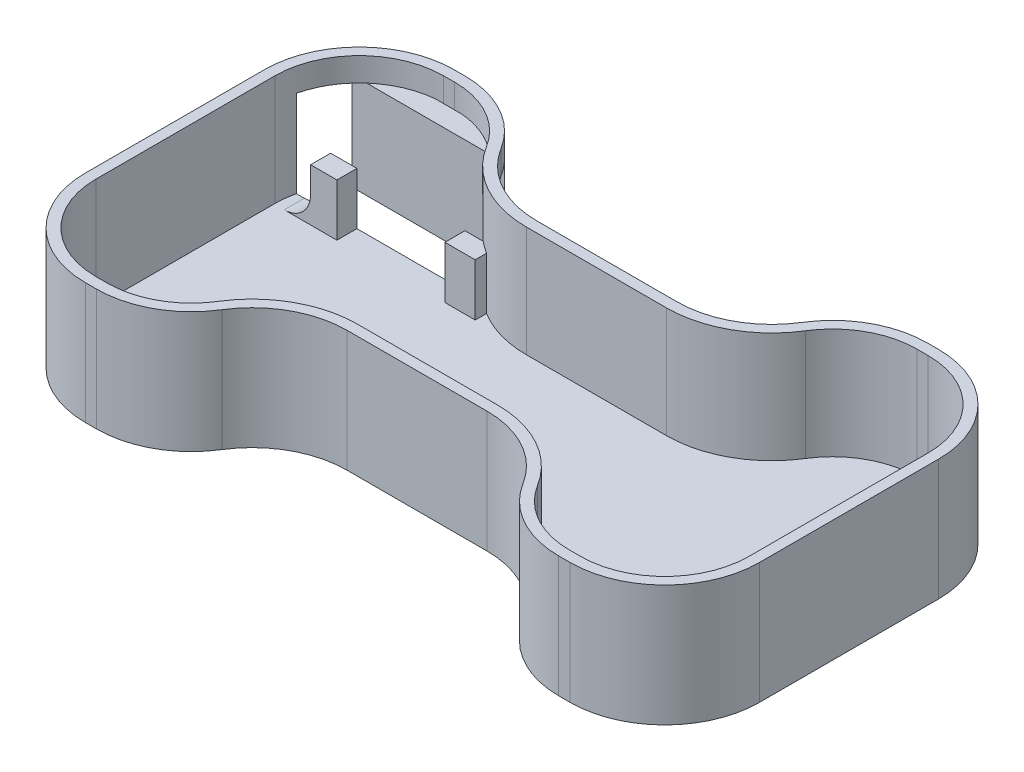
SolidWorks part; units mm, degrees
ref_plane "Front Plane" through (0, 0, 0) normal (0, 0, 1) x (1, 0, 0)
ref_plane "Top Plane" through (0, 0, 0) normal (0, 1, 0) x (1, 0, 0)
ref_plane "Right Plane" through (0, 0, 0) normal (1, 0, 0) x (0, 0, -1)
sketch "Sketch1" plane through (0, 0, 0) normal (0, 1, 0) x (1, 0, 0)
  line L0 (-128, 70) -> (-128, -70)
  line L1 (-128, 70) -> (-51.8, 70)
  line L2 (-51.8, 70) -> (-51.8, 36)
  line L3 (-51.8, 36) -> (51.8, 36)
  line L6 (51.8, 70) -> (51.8, 36)
  line L7 (128, 70) -> (51.8, 70)
  line L8 (128, 70) -> (128, -70)
  line L9 (-51.8, -70) -> (-51.8, -36)
  line L10 (-128, -70) -> (-51.8, -70)
  line L11 (128, -70) -> (51.8, -70)
  line L12 (51.8, -70) -> (51.8, -36)
  line L13 (-51.8, -36) -> (51.8, -36)
  dimension "D3" = 76.2
  dimension "D2" = 140
  dimension "D1" = 256
  dimension "D4" = 128
  dimension "D5" = 76.2
  dimension "D6" = 76.2
  dimension "D7" = 76.2
  dimension "D8" = 70
  dimension "D9" = 0
extrude "Boss-Extrude1" add sketch "Sketch1" along normal blind 4
fillet "Fillet2" radius 36 8 edges at (-51.8, 2, -70) (-128, 2, -70) (-128, 2, 70) (-51.8, 2, 70) (51.8, 2, -70) (128, 2, -70) (128, 2, 70) (51.8, 2, 70)
fillet "Fillet3" radius 36 4 edges at (-51.8, 2, -36) (-51.8, 2, 36) (51.8, 2, 36) (51.8, 2, -36)
sketch "Sketch2" plane through (0, 4, 0) normal (0, 1, 0) x (1, 0, 0)
  line L34 (-92, -66) -> (-87.7444, -66)
  line L35 (-87.7444, 66) -> (-92, 66)
  line L36 (-124, 34) -> (-124, -34)
  line L37 (-26.5889, -32) -> (26.5889, -32)
  line L50 (87.7444, -66) -> (92, -66)
  line L51 (124, -34) -> (124, 34)
  line L52 (92, 66) -> (87.7444, 66)
  line L53 (26.5889, 32) -> (-26.5889, 32)
  line L54 (-92, -66) -> (-87.7444, -66)
  line L55 (-87.7444, 66) -> (-92, 66)
  line L56 (-124, 34) -> (-124, -34)
  line L57 (-26.5889, -32) -> (26.5889, -32)
  line L58 (87.7444, -66) -> (92, -66)
  line L59 (124, -34) -> (124, 34)
  line L60 (92, 66) -> (87.7444, 66)
  line L61 (26.5889, 32) -> (-26.5889, 32)
  arc A24 (-124, -34) -> (-92, -66) centre (-92, -34) ccw
  arc A25 (-87.7444, -66) -> (-60.5642, -50.8889) centre (-87.7444, -34) ccw
  arc A26 (-92, 66) -> (-124, 34) centre (-92, 34) ccw
  arc A27 (-26.5889, -32) -> (-60.5642, -50.8889) centre (-26.5889, -72) ccw
  arc A28 (60.5642, -50.8889) -> (26.5889, -32) centre (26.5889, -72) ccw
  arc A29 (60.5642, -50.8889) -> (87.7444, -66) centre (87.7444, -34) ccw
  arc A30 (92, -66) -> (124, -34) centre (92, -34) ccw
  arc A31 (124, 34) -> (92, 66) centre (92, 34) ccw
  arc A32 (87.7444, 66) -> (60.5642, 50.8889) centre (87.7444, 34) ccw
  arc A33 (26.5889, 32) -> (60.5642, 50.8889) centre (26.5889, 72) ccw
  arc A34 (-60.5642, 50.8889) -> (-26.5889, 32) centre (-26.5889, 72) ccw
  arc A35 (-60.5642, 50.8889) -> (-87.7444, 66) centre (-87.7444, 34) ccw
  arc A36 (-124, -34) -> (-92, -66) centre (-92, -34) ccw
  arc A37 (-87.7444, -66) -> (-60.5642, -50.8889) centre (-87.7444, -34) ccw
  arc A38 (-92, 66) -> (-124, 34) centre (-92, 34) ccw
  arc A39 (-26.5889, -32) -> (-60.5642, -50.8889) centre (-26.5889, -72) ccw
  arc A40 (60.5642, -50.8889) -> (26.5889, -32) centre (26.5889, -72) ccw
  arc A41 (60.5642, -50.8889) -> (87.7444, -66) centre (87.7444, -34) ccw
  arc A42 (92, -66) -> (124, -34) centre (92, -34) ccw
  arc A43 (124, 34) -> (92, 66) centre (92, 34) ccw
  arc A44 (87.7444, 66) -> (60.5642, 50.8889) centre (87.7444, 34) ccw
  arc A45 (26.5889, 32) -> (60.5642, 50.8889) centre (26.5889, 72) ccw
  arc A46 (-60.5642, 50.8889) -> (-26.5889, 32) centre (-26.5889, 72) ccw
  arc A47 (-60.5642, 50.8889) -> (-87.7444, 66) centre (-87.7444, 34) ccw
  dimension "D1" = 4
extrude "Extrude-Thin1" add sketch "Sketch2" along normal blind 42 thin thin type one direction wall 4
sketch "Sketch3" plane through (0, 4, 0) normal (0, 1, 0) x (1, 0, 0)
  line L6 (-128, 58) -> (-38, 58)
  line L7 (-128, 58) -> (-128, 41.302)
  line L8 (-128, 41.302) -> (-38, 41.302)
  line L9 (-38, 58) -> (-38, 41.302)
  dimension "D1" = 16.698
  dimension "D2" = 90
  dimension "D3" = 7.302
extrude "Cut-Extrude1" cut sketch "Sketch3" against normal up to next and the other way blind 33
sketch "Sketch4" plane through (0, 4, 0) normal (0, 1, 0) x (1, 0, 0)
  line L1 (-59.1722, 33.702) -> (-47.6722, 33.702)
  line L2 (-59.1722, 33.702) -> (-59.1722, 41.302)
  line L3 (-59.1722, 41.302) -> (-47.6722, 41.302)
  line L4 (-47.6722, 33.702) -> (-47.6722, 41.302)
  line L5 (-110.1722, 41.302) -> (-100.1722, 41.302)
  line L6 (-110.1722, 41.302) -> (-110.1722, 33.702)
  line L7 (-110.1722, 33.702) -> (-100.1722, 33.702)
  line L8 (-100.1722, 41.302) -> (-100.1722, 33.702)
  line L9 (-113.166, 58) -> (-66.5784, 58) construction
  line L10 (-52.2332, 41.302) -> (-123.1558, 41.302) construction
  point P12 (-89.8722, 58)
  dimension "D1" = 10.3
  dimension "D2" = 10
  dimension "D3" = 11.5
  dimension "D4" = 41
  dimension "D5" = 0
  dimension "D6" = 0
  dimension "D7" = 7.6
  dimension "D8" = 7.6
extrude "Boss-Extrude2" add sketch "Sketch4" along normal blind 19.812
fillet "Fillet4" radius 10 1 edges at (-110.1722, 4, -37.502)
sketch "Sketch7" plane through (0, 4, 0) normal (0, 1, 0) x (1, 0, 0)
  line L0 (-113.166, 58) -> (-66.5784, 58)
  line L13 (-113.166, 58) -> (-113.166, 62.366)
  line L14 (-113.166, 62.366) -> (-107.166, 62.366)
  line L15 (-107.166, 62.366) -> (-107.166, 65.8618)
  line L16 (-107.166, 65.8618) -> (-73.166, 65.8618)
  line L17 (-73.166, 65.8618) -> (-73.166, 62.3618)
  line L18 (-73.166, 62.3618) -> (-66.5784, 62.3618)
  line L19 (-66.5784, 62.3618) -> (-66.5784, 58)
  dimension "D1" = 4.366
  dimension "D2" = 6
  dimension "D3" = 3.4958
  dimension "D4" = 34
  dimension "D5" = 3.5
extrude "Boss-Extrude3" add sketch "Sketch7" along normal blind 33
equation "\"7ç.000mm\"=7"
